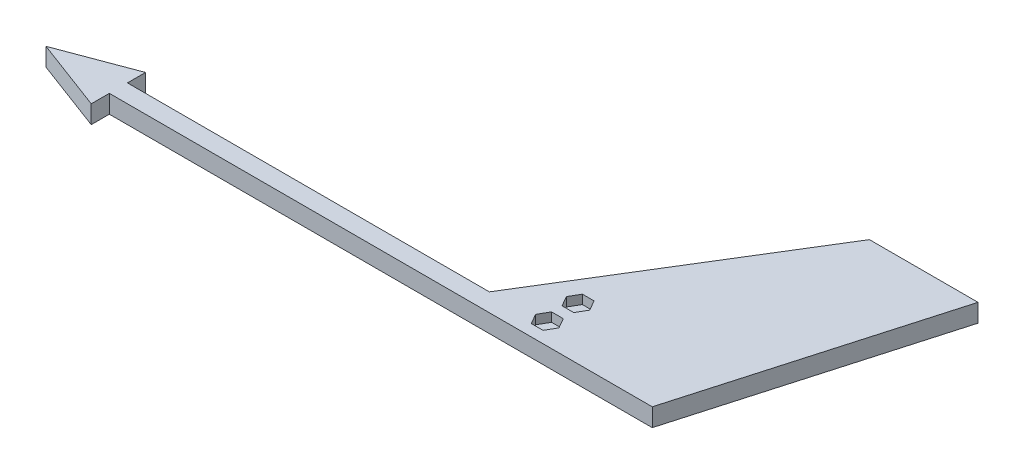
SolidWorks part; units mm, degrees
ref_plane "Front Plane" through (0, 0, 0) normal (0, 0, 1) x (1, 0, 0)
ref_plane "Top Plane" through (0, 0, 0) normal (0, 1, 0) x (1, 0, 0)
ref_plane "Right Plane" through (0, 0, 0) normal (1, 0, 0) x (0, 0, -1)
sketch "Sketch1" plane through (0, 0, 0) normal (0, 1, 0) x (1, 0, 0)
  line L0 (-20, 0) -> (0, 7.5)
  line L1 (-20, 0) -> (0, -7.5)
  line L2 (0, -7.5) -> (0, 7.5) construction
  line L3 (0, 7.5) -> (0, 2.5)
  line L4 (0, 2.5) -> (100, 2.5)
  line L5 (0, -7.5) -> (0, -2.5)
  line L6 (0, -2.5) -> (150, -2.5)
  line L7 (150, -2.5) -> (170, 67.5)
  line L8 (170, 67.5) -> (140, 67.5)
  line L9 (140, 67.5) -> (100, 2.5)
  point P2 (0, 0)
  dimension "D1" = 150
  dimension "D2" = 100
  dimension "D3" = 70
  dimension "D4" = 20
  dimension "D5" = 40
  dimension "D6" = 20
  dimension "D7" = 15
  dimension "D8" = 5
extrude "Boss-Extrude1" add sketch "Sketch1" along normal mid plane 5
sketch "Sketch2" plane through (0, 2.5, 0) normal (0, 1, 0) x (1, 0, 0)
  line L0 (118.2332, 12) -> (116.6166, 14.8)
  line L2 (116.6166, 14.8) -> (113.3834, 14.8)
  line L5 (113.3834, 9.2) -> (116.6166, 9.2)
  line L6 (116.6166, 9.2) -> (118.2332, 12)
  line L8 (113.3834, 14.8) -> (111.7668, 12)
  line L9 (111.7668, 12) -> (113.3834, 9.2)
  line L12 (0, -2.5) -> (150, -2.5) construction
  line L13 (118.2332, 3.5) -> (116.6166, 6.3)
  line L14 (116.6166, 6.3) -> (113.3834, 6.3)
  line L15 (113.3834, 6.3) -> (111.7668, 3.5)
  line L16 (111.7668, 3.5) -> (113.3834, 0.7)
  line L17 (113.3834, 0.7) -> (116.6166, 0.7)
  line L18 (116.6166, 0.7) -> (118.2332, 3.5)
  line L19 (118.2332, 12) -> (116.6166, 14.8) [skipped]
  line L20 (113.3834, 14.8) -> (111.7668, 12) [skipped]
  line L21 (111.7668, 12) -> (113.3834, 9.2) [skipped]
  circle A0 centre (115, 12) radius 2.8 construction
  circle A1 centre (115, 12) radius 2.8 construction
  circle A2 centre (115, 3.5) radius 2.8 construction
  point P1 (0, 0)
  point P19 (0, 0)
  dimension "D3" = 6
  dimension "D6" = 5.6
  dimension "D5" = 8.5
  dimension "D7" = 15
extrude "Cut-Extrude2" cut sketch "Sketch2" against normal blind 2.5
